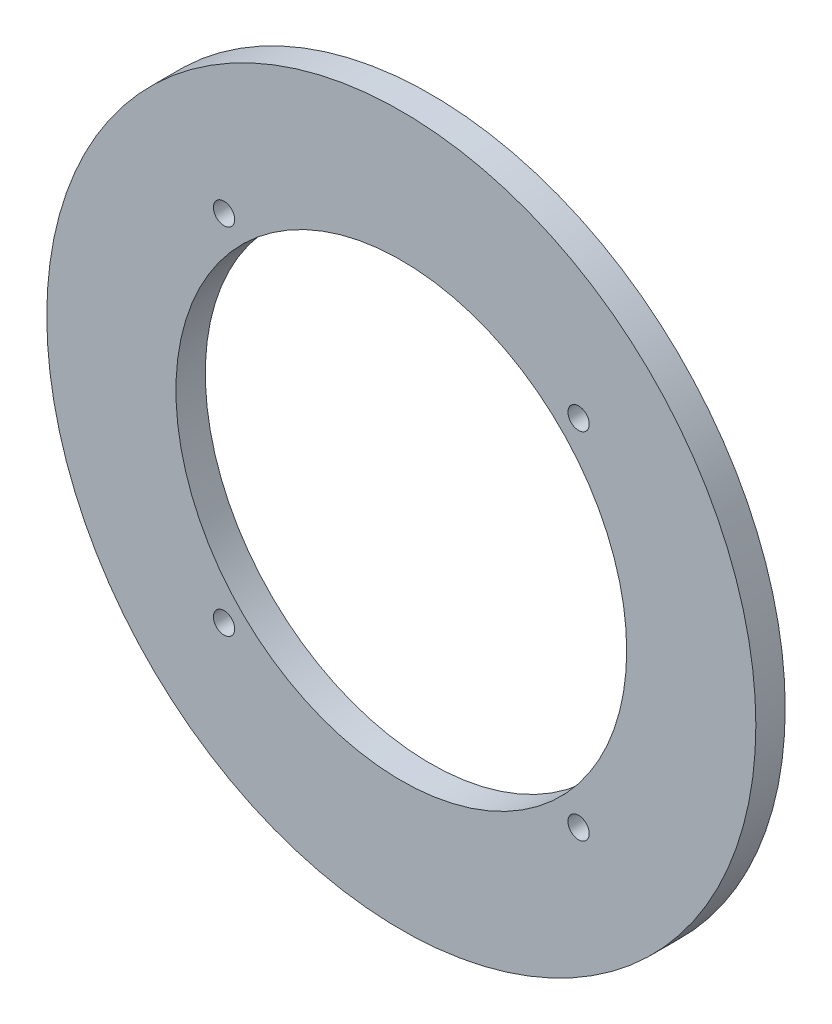
SolidWorks part; units mm, degrees
material "MC901"
ref_plane "正面" through (0, 0, 0) normal (0, 0, 1) x (1, 0, 0)
ref_plane "平面" through (0, 0, 0) normal (0, 1, 0) x (1, 0, 0)
ref_plane "右側面" through (0, 0, 0) normal (1, 0, 0) x (0, 0, -1)
sketch "ｽｹｯﾁ1" plane through (0, 0, 0) normal (0, 0, 1) x (1, 0, 0)
  circle A0 centre (0, 0) radius 44.5
  circle A1 centre (0, 0) radius 70
  dimension "D1" = 140
  dimension "D2" = 89
extrude "ﾎﾞｽ - 押し出し1" add sketch "ｽｹｯﾁ1" along normal blind 5.8
sketch "ｽｹｯﾁ2" plane through (0, 0, 5.8) normal (0, 0, 1) x (1, 0, 0)
  line L1 (-35, 35) -> (35, 35) construction
  line L2 (-35, 35) -> (-35, -35) construction
  line L3 (-35, -35) -> (35, -35) construction
  line L4 (35, 35) -> (35, -35) construction
  line L5 (-35, 35) -> (35, -35) construction
  line L6 (-35, -35) -> (35, 35) construction
  circle A0 centre (35, 35) radius 2.1
  circle A1 centre (35, -35) radius 2.1
  circle A2 centre (-35, -35) radius 2.1
  circle A3 centre (-35, 35) radius 2.1
  point P0 (0, 0)
  point P16 (0, 0)
  dimension "D3" = 4.2
  dimension "D1" = 70
  dimension "D2" = 70
  dimension "D4" = 4
extrude "ｶｯﾄ - 押し出し1" cut sketch "ｽｹｯﾁ2" against normal through all
